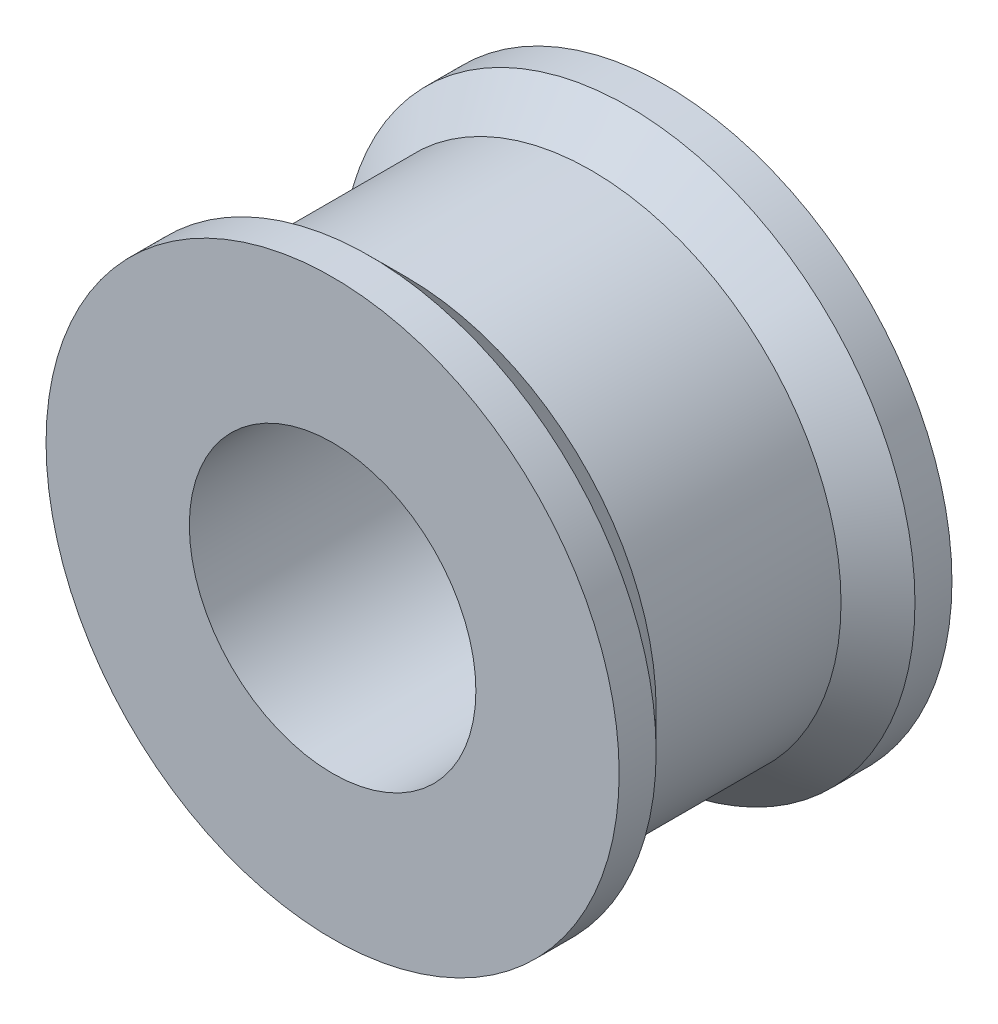
SolidWorks part; units mm, degrees
ref_plane "Front Plane" through (0, 0, 0) normal (0, 0, 1) x (1, 0, 0)
ref_plane "Top Plane" through (0, 0, 0) normal (0, 1, 0) x (1, 0, 0)
ref_plane "Right Plane" through (0, 0, 0) normal (1, 0, 0) x (0, 0, -1)
sketch "Sketch1" plane through (0, 0, 0) normal (0, 0, 1) x (1, 0, 0)
  circle A0 centre (0, 0) radius 3.875
  circle A1 centre (0, 0) radius 7.75
  dimension "D1" = 7.75
  dimension "D2" = 15.5
extrude "Boss-Extrude1" add sketch "Sketch1" along normal blind 1
sketch "Sketch2" plane through (0, 0, 1) normal (0, 0, 1) x (1, 0, 0)
  circle A0 centre (0, 0) radius 3.875
  circle A1 centre (0, 0) radius 6.75
  circle A2 centre (0, 0) radius 3.875 construction
  dimension "D1" = 13.5
extrude "Boss-Extrude2" add sketch "Sketch2" along normal blind 3.5
chamfer "Chamfer1" distance 1 angle 45 1 edges at (6.75, 0, 1)
mirror "Mirror5" about plane through (0, 0, 4.5) normal (0, 0, 1) of bodies 102
